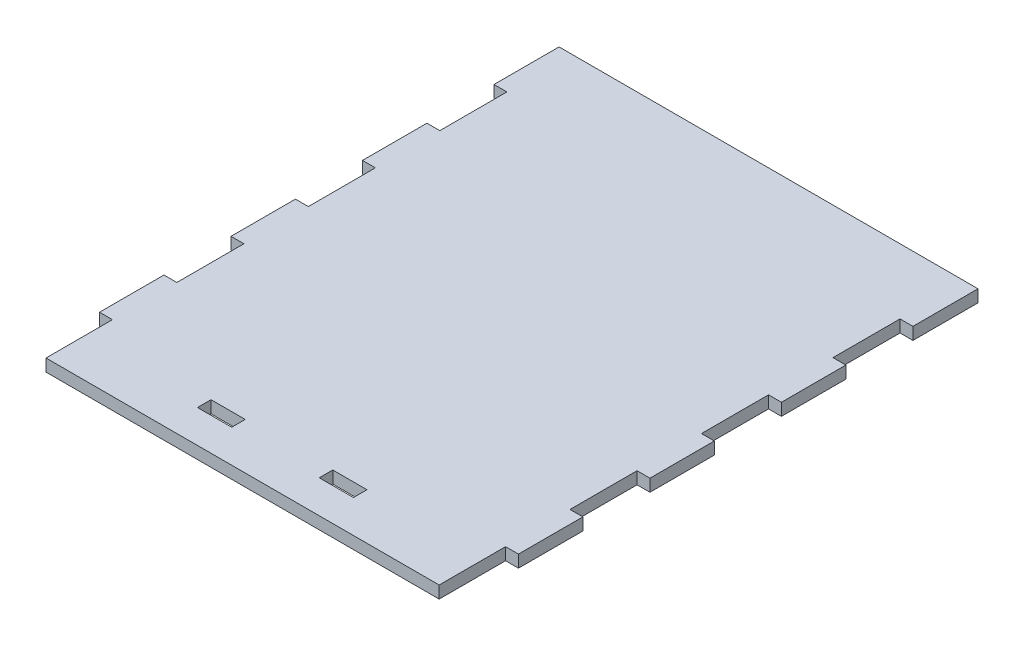
SolidWorks part; units mm, degrees
ref_plane "Front Plane" through (0, 0, 0) normal (0, 0, 1) x (1, 0, 0)
ref_plane "Top Plane" through (0, 0, 0) normal (0, 1, 0) x (1, 0, 0)
ref_plane "Right Plane" through (0, 0, 0) normal (1, 0, 0) x (0, 0, -1)
sketch "Sketch1" plane through (0, 0, 0) normal (0, 1, 0) x (1, 0, 0)
  line L0 (0, 0) -> (76.2, 0)
  line L1 (76.2, 12.7) -> (78.6892, 12.7)
  line L2 (78.6892, 12.7) -> (78.6892, 25.4)
  line L3 (78.6892, 25.4) -> (76.2, 25.4)
  line L4 (76.2, 25.4) -> (76.2, 38.1)
  line L5 (76.2, 38.1) -> (78.6892, 38.1)
  line L6 (78.6892, 38.1) -> (78.6892, 50.8)
  line L7 (78.6892, 50.8) -> (76.2, 50.8)
  line L8 (76.2, 50.8) -> (76.2, 63.5)
  line L9 (76.2, 63.5) -> (78.6892, 63.5)
  line L10 (78.6892, 63.5) -> (78.6892, 76.2)
  line L11 (78.6892, 76.2) -> (76.2, 76.2)
  line L12 (76.2, 76.2) -> (76.2, 88.9)
  line L13 (76.2, 88.9) -> (78.6892, 88.9)
  line L14 (78.6892, 88.9) -> (78.6892, 101.6)
  line L15 (78.6892, 101.6) -> (-2.4892, 101.6)
  line L16 (-2.4892, 101.6) -> (-2.4892, 88.9)
  line L17 (-2.4892, 88.9) -> (0, 88.9)
  line L18 (0, 88.9) -> (0, 76.2)
  line L19 (0, 76.2) -> (-2.4892, 76.2)
  line L20 (-2.4892, 76.2) -> (-2.4892, 63.5)
  line L21 (-2.4892, 63.5) -> (0, 63.5)
  line L22 (0, 63.5) -> (0, 50.8)
  line L23 (0, 50.8) -> (-2.4892, 50.8)
  line L24 (-2.4892, 50.8) -> (-2.4892, 38.1)
  line L25 (-2.4892, 38.1) -> (0, 38.1)
  line L26 (0, 38.1) -> (0, 25.4)
  line L27 (0, 25.4) -> (-2.4892, 25.4)
  line L28 (-2.4892, 25.4) -> (-2.4892, 12.7)
  line L29 (-2.4892, 12.7) -> (0, 12.7)
  line L30 (0, 12.7) -> (0, 0)
  line L31 (76.2, 12.7) -> (76.2, 0)
  line L32 (38.1, 0) -> (38.1, 101.6) construction
  dimension "D1" = 38.1
  dimension "D2" = 12.7
  dimension "D3" = 2.4892
extrude "Boss-Extrude1" add sketch "Sketch1" along normal blind 2.3622
sketch "Sketch2" plane through (0, 2.3622, 0) normal (0, 1, 0) x (1, 0, 0)
  line L0 (-2.4892, 101.6) -> (-2.4892, 88.9)
  line L1 (-2.4892, 88.9) -> (0, 88.9)
  line L2 (0, 88.9) -> (0, 76.2)
  line L3 (0, 76.2) -> (-2.4892, 76.2)
  line L4 (-2.4892, 76.2) -> (-2.4892, 63.5)
  line L5 (-2.4892, 63.5) -> (0, 63.5)
  line L6 (0, 63.5) -> (0, 50.8)
  line L7 (0, 50.8) -> (-2.4892, 50.8)
  line L8 (-2.4892, 50.8) -> (-2.4892, 38.1)
  line L9 (-2.4892, 38.1) -> (0, 38.1)
  line L10 (0, 38.1) -> (0, 25.4)
  line L11 (0, 25.4) -> (-2.4892, 25.4)
  line L12 (-2.4892, 25.4) -> (-2.4892, 12.7)
  line L15 (-2.4892, 12.7) -> (0, 12.7)
  line L16 (0, 12.7) -> (0, 0)
  line L17 (-2.3622, 101.6) -> (-2.3622, 89.027)
  line L18 (-2.3622, 89.027) -> (0.127, 89.027)
  line L19 (0.127, 89.027) -> (0.127, 76.073)
  line L20 (0.127, 76.073) -> (-2.3622, 76.073)
  line L21 (-2.3622, 76.073) -> (-2.3622, 63.627)
  line L22 (-2.3622, 63.627) -> (0.127, 63.627)
  line L23 (0.127, 63.627) -> (0.127, 50.673)
  line L24 (0.127, 50.673) -> (-2.3622, 50.673)
  line L25 (-2.3622, 50.673) -> (-2.3622, 38.227)
  line L26 (-2.3622, 38.227) -> (0.127, 38.227)
  line L27 (0.127, 38.227) -> (0.127, 25.273)
  line L28 (0.127, 25.273) -> (-2.3622, 25.273)
  line L29 (-2.3622, 25.273) -> (-2.3622, 12.827)
  line L30 (-2.3622, 12.827) -> (0.127, 12.827)
  line L31 (0.127, 12.827) -> (0.127, 0)
  line L32 (0, 0) -> (0.127, 0)
  line L33 (-2.3622, 101.6) -> (-2.4892, 101.6)
  line L34 (38.1, 101.6) -> (38.1, 0) construction
  line L35 (78.6892, 101.6) -> (-2.4892, 101.6) construction
  line L36 (0, 0) -> (76.2, 0) construction
  line L37 (78.5622, 101.6) -> (78.6892, 101.6)
  line L38 (76.2, 0) -> (76.073, 0)
  line L39 (76.073, 12.827) -> (76.073, 0)
  line L40 (78.5622, 12.827) -> (76.073, 12.827)
  line L41 (78.5622, 25.273) -> (78.5622, 12.827)
  line L42 (76.073, 25.273) -> (78.5622, 25.273)
  line L43 (76.073, 38.227) -> (76.073, 25.273)
  line L44 (78.5622, 38.227) -> (76.073, 38.227)
  line L45 (78.5622, 50.673) -> (78.5622, 38.227)
  line L46 (76.073, 50.673) -> (78.5622, 50.673)
  line L47 (76.073, 63.627) -> (76.073, 50.673)
  line L48 (78.5622, 63.627) -> (76.073, 63.627)
  line L49 (78.5622, 76.073) -> (78.5622, 63.627)
  line L50 (76.073, 76.073) -> (78.5622, 76.073)
  line L51 (76.073, 89.027) -> (76.073, 76.073)
  line L52 (78.5622, 89.027) -> (76.073, 89.027)
  line L53 (78.5622, 101.6) -> (78.5622, 89.027)
  line L54 (76.2, 12.7) -> (76.2, 0)
  line L55 (78.6892, 12.7) -> (76.2, 12.7)
  line L56 (78.6892, 25.4) -> (78.6892, 12.7)
  line L57 (76.2, 25.4) -> (78.6892, 25.4)
  line L58 (76.2, 38.1) -> (76.2, 25.4)
  line L59 (78.6892, 38.1) -> (76.2, 38.1)
  line L60 (78.6892, 50.8) -> (78.6892, 38.1)
  line L61 (76.2, 50.8) -> (78.6892, 50.8)
  line L62 (76.2, 63.5) -> (76.2, 50.8)
  line L63 (78.6892, 63.5) -> (76.2, 63.5)
  line L64 (78.6892, 76.2) -> (78.6892, 63.5)
  line L65 (76.2, 76.2) -> (78.6892, 76.2)
  line L66 (76.2, 88.9) -> (76.2, 76.2)
  line L67 (78.6892, 88.9) -> (76.2, 88.9)
  line L68 (78.6892, 101.6) -> (78.6892, 88.9)
  line M1 (76.2, 0) -> (76.2, 12.7)
  line M2 (76.2, 12.7) -> (78.6892, 12.7)
  line M3 (78.6892, 12.7) -> (78.6892, 25.4)
  line M4 (78.6892, 25.4) -> (76.2, 25.4)
  line M5 (76.2, 25.4) -> (76.2, 38.1)
  line M6 (76.2, 38.1) -> (78.6892, 38.1)
  line M7 (78.6892, 38.1) -> (78.6892, 50.8)
  line M8 (78.6892, 50.8) -> (76.2, 50.8)
  line M9 (76.2, 50.8) -> (76.2, 63.5)
  line M10 (76.2, 63.5) -> (78.6892, 63.5)
  line M11 (78.6892, 63.5) -> (78.6892, 76.2)
  line M12 (78.6892, 76.2) -> (76.2, 76.2)
  line M13 (76.2, 76.2) -> (76.2, 88.9)
  line M14 (76.2, 88.9) -> (78.6892, 88.9)
  line M15 (78.6892, 88.9) -> (78.6892, 101.6)
  line M16 (78.6892, 101.6) -> (-2.4892, 101.6)
  line M17 (-2.4892, 101.6) -> (-2.4892, 88.9)
  line M18 (-2.4892, 88.9) -> (0, 88.9)
  line M19 (0, 88.9) -> (0, 76.2)
  line M20 (0, 76.2) -> (-2.4892, 76.2)
  line M21 (-2.4892, 76.2) -> (-2.4892, 63.5)
  line M22 (-2.4892, 63.5) -> (0, 63.5)
  line M23 (0, 63.5) -> (0, 50.8)
  line M24 (0, 50.8) -> (-2.4892, 50.8)
  line M25 (-2.4892, 50.8) -> (-2.4892, 38.1)
  line M26 (-2.4892, 38.1) -> (0, 38.1)
  line M27 (0, 38.1) -> (0, 25.4)
  line M28 (0, 25.4) -> (-2.4892, 25.4)
  line M29 (-2.4892, 25.4) -> (-2.4892, 12.7)
  line M30 (-2.4892, 12.7) -> (0, 12.7)
  line M31 (0, 12.7) -> (0, 0)
  line M32 (0, 0) -> (76.2, 0)
  dimension "D1" = 0.127
extrude "Cut-Extrude1" cut sketch "Sketch2" against normal through all contours L53 L52 L51 L50 L49 L48 L47 L46 L45 L44 L43 L42 L41 L40 L39 M16 M32 M1 M2 M3 M4 M5 M6 M7 M8 M9 M10 M11 M12 M13 M14 M15 | L31 L30 L29 L28 L27 L26 L25 L24 L23 L22 L21 L20 L19 L18 L17 M16 M17 M18 M19 M20 M21 M22 M23 M24 M25 M26 M27 M28 M29 M30 M31 M32 region at (-2.4257, 2.3622, -100.5837) region at (78.6257, 2.3622, -100.5837)
sketch "Sketch3" plane through (0, 0, 0) normal (0, -1, 0) x (1, 0, 0)
  line L0 (0.127, -6.35) -> (76.073, -6.35) construction
  line L1 (0.127, -12.827) -> (0.127, 0) construction
  line L2 (76.073, -12.827) -> (76.073, 0) construction
  line L3 (0.127, 0) -> (76.073, 0) construction
  line L4 (38.1, 0) -> (38.1, -101.6) construction
  line L5 (23.0378, -6.35) -> (29.6418, -6.35)
  line L6 (23.0378, -6.35) -> (23.0378, -8.9662)
  line L7 (23.0378, -8.9662) -> (29.6418, -8.9662)
  line L8 (29.6418, -6.35) -> (29.6418, -8.9662)
  line L9 (78.5622, -101.6) -> (-2.3622, -101.6) construction
  line L10 (-2.3622, -25.273) -> (-2.3622, -12.827) construction
  line L11 (46.5582, -6.35) -> (46.5582, -8.9662)
  line L12 (53.1622, -8.9662) -> (46.5582, -8.9662)
  line L13 (53.1622, -6.35) -> (53.1622, -8.9662)
  line L14 (53.1622, -6.35) -> (46.5582, -6.35)
  dimension "D1" = 6.35
  dimension "D2" = 6.604
  dimension "D3" = 2.6162
  dimension "D4" = 25.4
extrude "Cut-Extrude2" cut sketch "Sketch3" against normal through all
